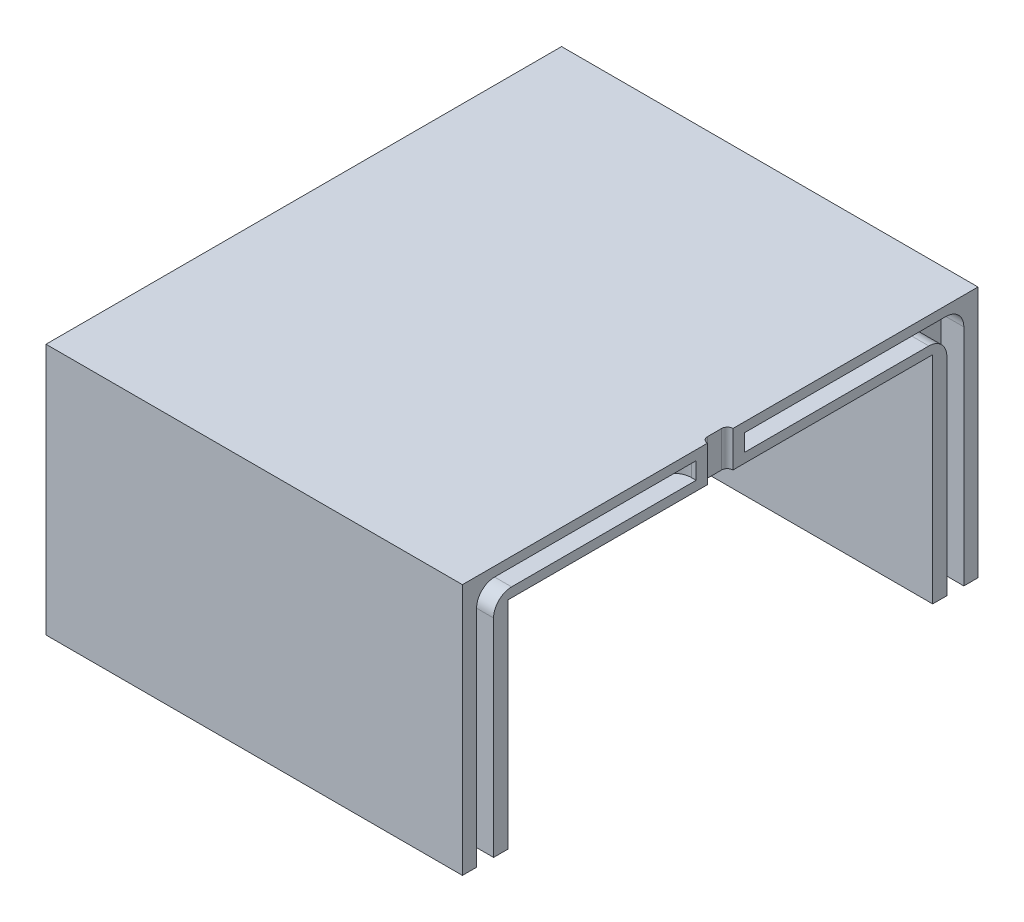
SolidWorks part; units mm, degrees
material "6061 Alloy"
ref_plane "Front Plane" through (0, 0, 0) normal (0, 0, 1) x (1, 0, 0)
ref_plane "Top Plane" through (0, 0, 0) normal (0, 1, 0) x (1, 0, 0)
ref_plane "Right Plane" through (0, 0, 0) normal (1, 0, 0) x (0, 0, -1)
sketch "MainSketch" plane through (0, 0, 0) normal (0, 1, 0) x (1, 0, 0)
  line L0 (0, -4) -> (-32.75, -4)
  line L1 (0, 0) -> (-36.75, 0)
  line L2 (0, 0) -> (0, -45.5)
  line L3 (0, -45.5) -> (-36.75, -45.5)
  line L4 (-36.75, 0) -> (-36.75, -45.5)
  line L5 (-32.75, -4) -> (-32.75, -41.5)
  line L6 (-32.75, -41.5) -> (0, -41.5)
  line L7 (31.75, -5) -> (-31.75, -5) construction
  line L8 (-31.75, -5) -> (-31.75, -40.5) construction
  line L9 (-31.75, -40.5) -> (31.75, -40.5) construction
  line L10 (0, -22.125) -> (0, -23.375) construction
  line L11 (0.5, -22.125) -> (0.5, -23.375)
  line L12 (-0.5, -22.125) -> (-0.5, -23.375)
  arc A0 (0.5, -22.125) -> (-0.5, -22.125) centre (0, -22.125) ccw
  arc A1 (-0.5, -23.375) -> (0.5, -23.375) centre (0, -23.375) ccw
  point P7 (-10, -2.5)
  point P10 (-34.25, -2.5)
  point P11 (-34.25, -43)
  point P12 (-10, -43)
  point P17 (0, -22.75)
  point P24 (-18.375, -2.5)
  point P25 (-18.375, -43)
  point P26 (0, 0)
  point P27 (0, 0)
  point P28 (0, 0)
  dimension "D14" = 0.5
  dimension "D1" = 4
  dimension "D2" = 4
  dimension "D3" = 4
  dimension "D4" = 36.75
  dimension "D6" = 5
  dimension "D7" = 5
  dimension "D8" = 5
  dimension "D9" = 2.5
  dimension "D10" = 2.5
  dimension "D11" = 10
  dimension "D12" = 10
  dimension "D13" = 2.5
  dimension "D15" = 1.25
  dimension "D5" = 35.5
  dimension "D16" = 63.5
  dimension "D17" = 18.375
extrude "Wall" add sketch "MainSketch" along normal blind 19.05 contours L6 L5 L0 L2 L1 L4 L3 region at (-16.375, 0, 3.4151)
extrude "Roof" add sketch "MainSketch<3>" along normal blind 3.175 from surface contours L5 L6 L2 L0 | L6 L5 L0 L2 L1 L4 L3 region at (-16.3884, 0, 22.75) region at (-16.375, 0, 3.4151) starting at face at (-17.375, 19.05, 22.75)
sketch "MainSketch<3>" plane through (0, 0, 0) normal (0, 1, 0) x (1, 0, 0) same geometry as "MainSketch"
hole_wizard "#2-56 Tapped Hole1" positions "3DSketch1" profile "Sketch2" tap size "#2-56" standard "ANSI Inch"
sketch3d "3DSketch1"
  point P19 (-18.375, 0, 2.5)
  point P22 (-18.375, 0, 43)
  point P26 (0, 0, 0)
sketch "Sketch2" plane through (-18.375, 0, 2.5) normal (1, 0, 0) x (0, 0, -1)
  line L0 (0, 0) -> (0, 6.2642)
  line L1 (0, 6.2642) -> (0.889, 5.73)
  line L2 (0.889, 5.73) -> (0.889, 0)
  line L5 (0.889, 0) -> (0, 0)
  line L10 (0, 6.2642) -> (-0.889, 5.73) construction
  line L11 (0, -6.35) -> (0, 107.95) construction
  dimension "Tap Drill Dia." = 1.778
  dimension "Tap Drill Depth" = 5.73
  dimension "Drill Angle" = 118
cosmetic thread "Hole Thread1" parameters "D1"=4.37, "D2"=2.1844
cosmetic thread "Hole Thread2" parameters "D1"=4.37, "D2"=2.1844
sketch "Sketch3" plane through (0, 0, 0) normal (1, 0, 0) x (0, 0, -1)
  line L0 (-44.25, 0) -> (-44.25, 21.3875)
  line L1 (-41.5, 0) -> (-45.5, 0) construction
  line L2 (-44.25, 21.3875) -> (-1.25, 21.3875)
  line L3 (-1.25, 21.3875) -> (-1.25, 0)
  line L4 (0, 0) -> (-4, 0) construction
  line L5 (-42.75, 0) -> (-42.75, 19.8875)
  line L6 (-42.75, 19.8875) -> (-2.75, 19.8875)
  line L7 (-2.75, 19.8875) -> (-2.75, 0)
  line L8 (-44.25, 0) -> (-42.75, 0) construction
  line L9 (-45.5, 22.225) -> (-45.5, 0) construction
  line L10 (-2.75, 0) -> (-1.25, 0)
  line L11 (0, 22.225) -> (0, 0) construction
  line L12 (-22.75, 21.3875) -> (-22.75, 19.8875) construction
  line L13 (-21.625, 22.225) -> (0, 22.225) construction
  line L14 (-23.875, 22.225) -> (-23.875, 19.05) construction
  line L15 (-44.25, 0) -> (-42.75, 0)
  line L16 (-24.875, 21.3875) -> (-24.875, 19.8875)
  line L17 (-20.625, 21.3875) -> (-20.625, 19.8875)
  line L20 (-21.625, 22.225) -> (-21.625, 19.05) construction
  point P10 (-43.5, 0)
  point P15 (-2, 0)
  point P20 (-22.75, 20.6375)
  dimension "D1" = 1.5
  dimension "D2" = 1.5
  dimension "D3" = 1.5
  dimension "D4" = 2
  dimension "D5" = 2
  dimension "D6" = 1.5875
  dimension "D7" = 1
  dimension "D8" = 1
extrude "2mm depth cut" cut sketch "Sketch3" against normal blind 2 contours L16 L2 L0 L15 L5 L6 | L2 L17 L6 L7 L10 L3 region at (0, 10.6937, 43.9614) region at (0, 21.0989, 10.9375)
fillet "1/16 in fillet" radius 1.5875 6 edges at (-1, 21.3875, 44.25) (-1, 19.8875, 42.75) (-1, 19.8875, 2.75) (-1, 21.3875, 1.25) (-2, 20.6375, 24.875) (-2, 20.6375, 20.625)
equation "\"D2@MainSketch\" = \"D1@MainSketch\""
equation "\"D3@MainSketch\" = \"D2@MainSketch\""
equation "\"D7@MainSketch\" = \"D6@MainSketch\""
equation "\"D8@MainSketch\" = \"D6@MainSketch\""
equation "\"D9@MainSketch\" = \"D7@MainSketch\" / 2"
equation "\"D10@MainSketch\" = \"D9@MainSketch\""
equation "\"D12@MainSketch\" = \"D11@MainSketch\""
equation "\"D13@MainSketch\" = \"D10@MainSketch\""
equation "\"D4@MainSketch\"=(\"D16@MainSketch\"+\"D6@MainSketch\"*2)/2"
equation "\"D3@Sketch3\"=\"D2@Sketch3\""
equation "\"D1@Sketch3\"=\"D3@Sketch3\""
equation "\"D5@Sketch3\"=\"D4@Sketch3\""
equation "\"side_thick\"= 4"
equation "\"D1@MainSketch\"=\"side_thick\""
equation "\"top_thick\"=3.175"
equation "\"D1@Roof\"=\"top_thick\""
equation "\"D6@Sketch3\"=\"top_thick\"/2"
equation "\"D4@Sketch3\"=\"side_thick\"/2"
equation "\"D8@Sketch3\"=\"D7@Sketch3\""
equation "\"D17@MainSketch\"=\"D4@MainSketch\"/2"
